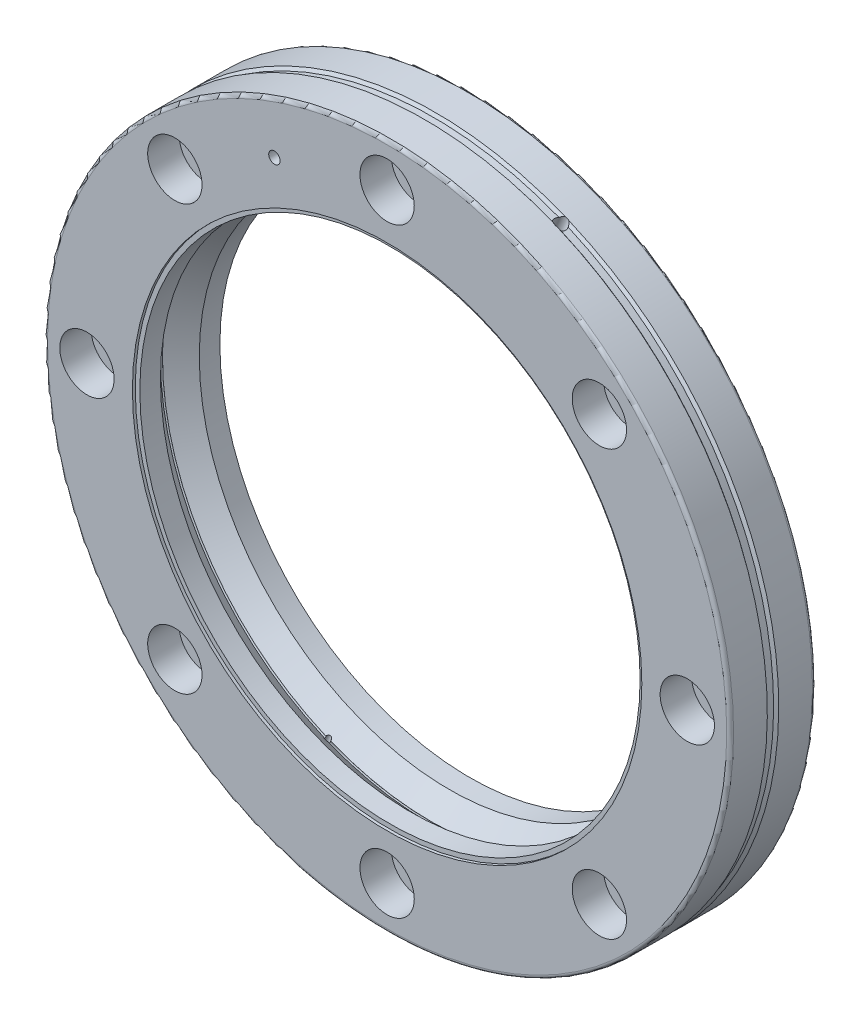
SolidWorks part; units mm, degrees
ref_plane "前视基准面" through (0, 0, 0) normal (0, 0, 1) x (1, 0, 0)
ref_plane "上视基准面" through (0, 0, 0) normal (0, 1, 0) x (1, 0, 0)
ref_plane "右视基准面" through (0, 0, 0) normal (1, 0, 0) x (0, 0, -1)
sketch "草图1" plane through (0, 0, 0) normal (0, 0, 1) x (1, 0, 0)
  circle A0 centre (0, 0) radius 43.75
  circle A1 centre (0, 0) radius 60
  dimension "D1" = 120
  dimension "D2" = 87.5
extrude "凸台-拉伸1" add sketch "草图1" along normal mid plane 15
sketch "草图2" plane through (0, 0, 0) normal (1, 0, 0) x (0, 0, -1)
  line L0 (0, 0) -> (0, 30.1811) construction
  line L1 (-3.5355, 43.61) -> (-0.1768, 46.9688)
  line L2 (0.1768, 46.9688) -> (3.5355, 43.61)
  line L3 (3.5355, 43.61) -> (-3.5355, 43.61)
  line L4 (-1, 60) -> (1, 60)
  line L5 (1, 60) -> (0.6, 59.5)
  line L6 (0.6, 59.5) -> (-0.6, 59.5)
  line L7 (-0.6, 59.5) -> (-1, 60)
  line L8 (-12.5536, 0) -> (14.1239, 0) construction
  arc A0 (0.1768, 46.9688) -> (-0.1768, 46.9688) centre (0, 47.1455) ccw
  dimension "D3" = 0.5
  dimension "D1" = 5
  dimension "D2" = 43.61
  dimension "D4" = 45
  dimension "D6" = 60
  dimension "D7" = 0.5
  dimension "D8" = 2
  dimension "D9" = 1.2
revolve "切除-旋转1" cut sketch "草图2" angle 360 about L8
fillet "圆角1" radius 0.6 2 edges at (60, 0, -7.5) (60, 0, 7.5)
hole_wizard "M1.6 六角头螺栓的柱形沉头孔1" positions "草图3" profile "草图4" counterbore size "M1.6" standard "GB" end condition through all
sketch "草图3" plane through (0, 0, 7.5) normal (0, 0, 1) x (1, 0, 0)
  line L1 (0, 31.2321) -> (0, -1.1171) construction
  point P0 (0, 52.5)
  dimension "D1" = 52.5
sketch "草图4" plane through (0, 52.5, 7.5) normal (1, 0, 0) x (0, -1, 0)
  line L0 (0, 0) -> (0, 15)
  line L1 (0, 15) -> (2.8, 15)
  line L3 (2.8, 15) -> (2.8, 5.5)
  line L4 (2.8, 5.5) -> (4.75, 5.5)
  line L5 (4.75, 5.5) -> (4.75, 0)
  line L7 (4.75, 0) -> (0, 0)
  line L11 (0, -6.35) -> (0, 107.95) construction
  dimension "通孔孔直径" = 5.6
  dimension "通孔孔深度" = 15
  dimension "柱形沉头孔直径" = 9.5
  dimension "柱形沉头孔深度" = 5.5
pattern_circular "阵列(圆周)1" count 8 over 360 about axis through (0, 0, 7.5) along (0, 0, -1) of "M1.6 六角头螺栓的柱形沉头孔1"
ref_axis "基准轴1" through (0, 0, 6.9) along (0, 0, -1)
ref_plane "基准面1" through (0, 0, 0) normal (0.3827, 0.9239, 0) x (0, 0, -1)
sketch "草图7" plane through (0, 0, 0) normal (0.3827, 0.9239, 0) x (0, 0, -1)
  circle A0 centre (0, 0) radius 1.05
  dimension "D1" = 2.1
extrude "切除-拉伸1" cut sketch "草图7" against normal blind 5 from offset 60
sketch "草图8" plane through (21.0476, 50.8134, 0) normal (0.3827, 0.9239, 0) x (0.9239, -0.3827, 0)
  circle A0 centre (0, 0) radius 0.5
  dimension "D1" = 1
extrude "切除-拉伸2" cut sketch "草图8" against normal blind 15
pattern_circular "阵列(圆周)2" count 2 over 360 about axis through (0, 0, 7.5) along (0, 0, -1) of "切除-拉伸1", "切除-拉伸2"
sketch "草图9" plane through (0, 0, 7.5) normal (0, 0, 1) x (1, 0, 0)
  circle A0 centre (0, 0) radius 44.55
  circle A1 centre (0, 0) radius 43.75 construction
  dimension "D1" = 0.8
extrude "切除-拉伸3" cut sketch "草图9" against normal blind 0.5
mirror "镜向1" about plane through (0, 0, 0) normal (0, 0, 1) of "切除-拉伸3"
sketch "草图10" plane through (0, 0, 7.5) normal (0, 0, 1) x (1, 0, 0)
  line L0 (0, 52.5) -> (0, 0) construction
  line L1 (0, 0) -> (-19.7082, 47.5798) construction
  circle A0 centre (-19.7082, 47.5798) radius 1
  dimension "D3" = 2
  dimension "D1" = 22.5
  dimension "D2" = 51.5
extrude "切除-拉伸4" cut sketch "草图10" against normal through all draft 1.14
